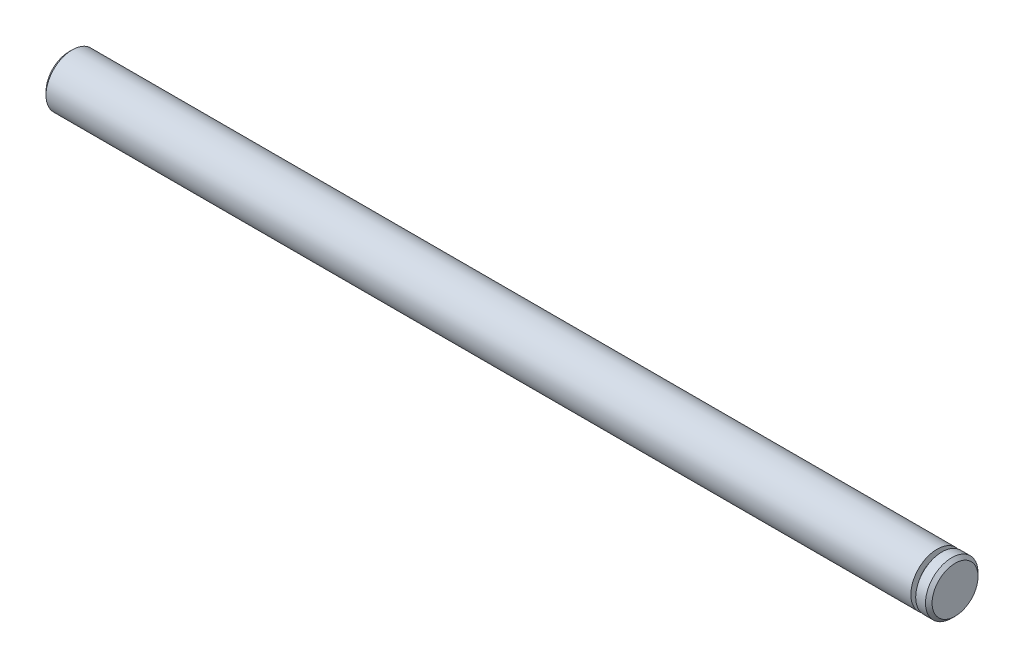
SolidWorks part; units mm, degrees
material "6061-T6 (SS)"
ref_plane "Front" through (0, 0, 0) normal (0, 0, 1) x (1, 0, 0)
ref_plane "Top" through (0, 0, 0) normal (0, 1, 0) x (1, 0, 0)
ref_plane "Right" through (0, 0, 0) normal (1, 0, 0) x (0, 0, -1)
ref_axis "side-side" through (80.9, 0, 0) along (-1, 0, 0)
ref_axis "up-down" through (0, 50, 0) along (0, -1, 0)
ref_axis "front-back" through (0, 0, -80.9) along (0, 0, 1)
sketch "Sketch1" plane through (0, 0, 0) normal (0, 0, 1) x (1, 0, 0)
  line L0 (0.7366, 4) -> (2.7366, 4)
  line L1 (-132.2634, 0) -> (2.7366, 0)
  line L2 (-132.2634, 0) -> (-132.2634, 4)
  line L3 (-132.2634, 4) -> (0, 4)
  line L4 (2.7366, 0) -> (2.7366, 4)
  line L6 (0.7366, 4) -> (0.7366, 3)
  line L7 (0.7366, 3) -> (0, 3)
  line L8 (0, 4) -> (0, 3)
  line L9 (2.7366, 0) -> (11.0753, 0) construction
  dimension "D1" = 135
  dimension "D2" = 0.7366
  dimension "D3" = 6
  dimension "D4" = 8
  dimension "D5" = 2
revolve "Revolve1" add sketch "Sketch1" angle 360 about L9
chamfer "Chamfer1" distance 0.5 angle 45 2 edges at (-132.2634, 0, 4) (2.7366, 0, 4)
